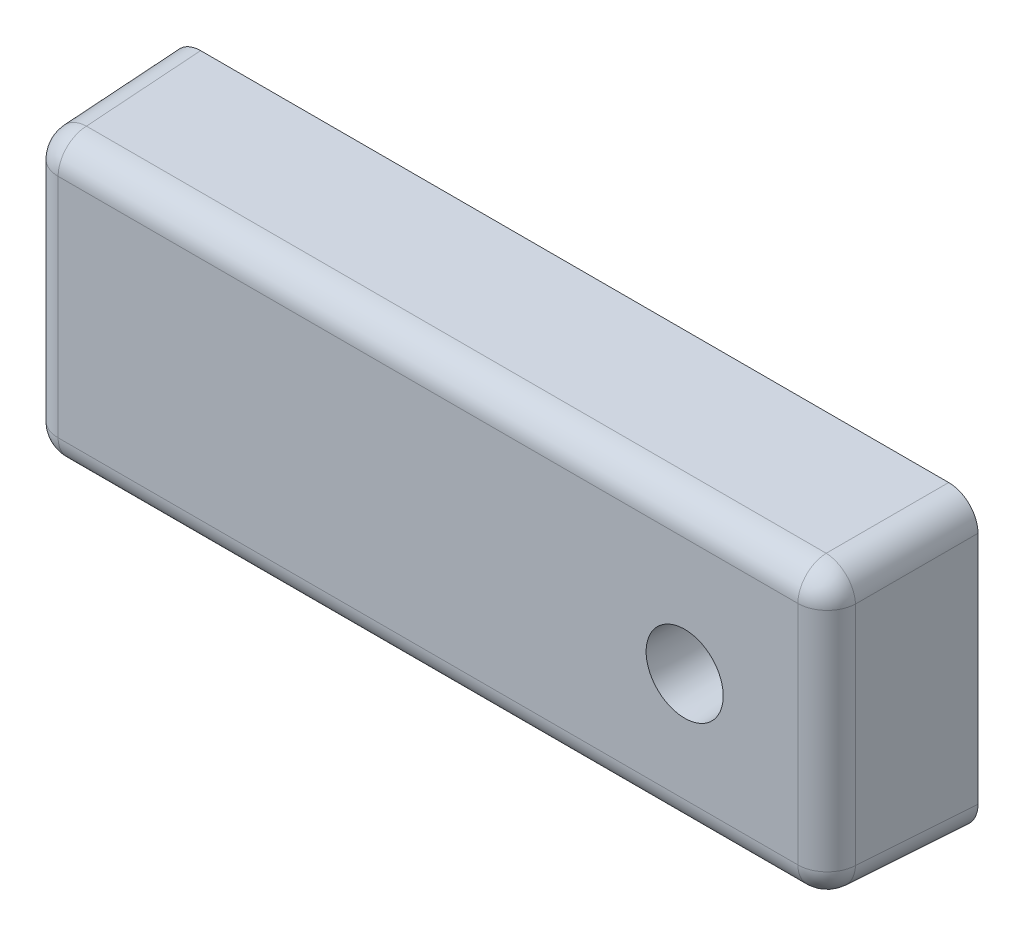
SolidWorks part; units mm, degrees
ref_plane "Front Plane" through (0, 0, 0) normal (0, 0, 1) x (1, 0, 0)
ref_plane "Top Plane" through (0, 0, 0) normal (0, 1, 0) x (1, 0, 0)
ref_plane "Right Plane" through (0, 0, 0) normal (1, 0, 0) x (0, 0, -1)
sketch "Sketch1" plane through (0, 0, 0) normal (0, 0, 1) x (1, 0, 0)
  line L1 (-13, 2.7505) -> (-68, 2.7505)
  line L2 (-13, 2.7505) -> (-13, 22.7505)
  line L3 (-13, 22.7505) -> (-68, 22.7505)
  line L4 (-68, 2.7505) -> (-68, 22.7505)
  circle A0 centre (-22.9998, 12.4582) radius 2.2792 construction
  circle A1 centre (-22.9998, 12.4582) radius 2.2792
  spline S0 degree 3 poles (-22.91, 10.1824) (-22.4605, 10.2302) (-22.1691, 10.3218) (-21.7781, 10.5356) (-21.6534, 10.6204) (-21.4236, 10.8124) (-21.3196, 10.9185) (-21.1329, 11.1504) (-21.0496, 11.2774) (-20.9115, 11.5412) (-20.8558, 11.6789) (-20.7715, 11.9661) (-20.7433, 12.1144) (-20.7165, 12.4102) (-20.7175, 12.5597) (-20.7495, 12.8588) (-20.7797, 13.0045) (-20.8679, 13.2884) (-20.9269, 13.428) (-21.0698, 13.6903) (-21.1532, 13.8133) (-21.3439, 14.0427) (-21.452, 14.1492) (-21.799, 14.4297) (-22.0699, 14.5722) (-22.4973, 14.6982) (-22.6453, 14.7267) (-22.9437, 14.7538) (-23.0923, 14.7525) (-23.3883, 14.721) (-23.5369, 14.6902) (-23.8213, 14.6014) (-23.9581, 14.5435) (-24.2207, 14.4002) (-24.3456, 14.3151) (-24.5737, 14.1248) (-24.6784, 14.0185) (-24.8673, 13.7842) (-24.9488, 13.6596) (-25.0869, 13.3965) (-25.1438, 13.2561) (-25.2281, 12.9694) (-25.2559, 12.8234) (-25.2831, 12.5265) (-25.2819, 12.3746) (-25.2347, 11.9308) (-25.144, 11.6386) (-24.8602, 11.1166) (-24.6649, 10.8811) (-24.318, 10.6003) (-24.1913, 10.5167) (-23.9276, 10.3779) (-23.79, 10.322) (-23.5034, 10.2372) (-23.3548, 10.2087) (-23.0589, 10.1815) (-22.91, 10.1824) (-22.4605, 10.2302) (-22.1691, 10.3218) knots -0.03125 -0.03125 0 0 0.0625 0.0625 0.09375 0.09375 0.125 0.125 0.15625 0.15625 0.1875 0.1875 0.21875 0.21875 0.25 0.25 0.28125 0.28125 0.3125 0.3125 0.34375 0.34375 0.375 0.375 0.4375 0.4375 0.46875 0.46875 0.5 0.5 0.53125 0.53125 0.5625 0.5625 0.59375 0.59375 0.625 0.625 0.65625 0.65625 0.6875 0.6875 0.71875 0.71875 0.75 0.75 0.8125 0.8125 0.875 0.875 0.90625 0.90625 0.9375 0.9375 0.96875 0.96875 1 1 1.0625 1.0625 1.09375 only from (-22.7602, 10.1984) to (-22.7602, 10.1984) construction
  dimension "D1" = 9.7602
  dimension "D2" = 7.4479
  dimension "D3" = 20
  dimension "D4" = 55
  dimension "D5" = 9.7077
  dimension "D6" = 9.9998
extrude "Boss-Extrude1" add sketch "Sketch1" along normal blind 10 draft 2
fillet "Fillet1" radius 2 4 edges at (-40.5, 3.0997, 10) (-67.6508, 12.7505, 10) (-40.5, 22.4013, 10) (-13.3492, 12.7505, 10)
fillet "Fillet2" radius 2 8 edges at (-13.8913, 21.8592, 9.4387) (-67.1087, 21.8592, 9.4387) (-13.8913, 3.6417, 9.4387) (-67.1087, 3.6417, 9.4387) (-13.1409, 22.6096, 4.0349) (-67.8591, 22.6096, 4.0349) (-13.1409, 2.8914, 4.0349) (-67.8591, 2.8914, 4.0349)
scale "Scale1"
other "Parting Line2"
other "Shut-Off Surface2"
other "Parting Surface2" parameters "D1"=42.2
sketch "Sketch3" plane through (0, 0, -2.453) normal (0, 0, -1) x (-1, 0, 0)
  line L1 (96.8339, -29.4991) -> (-15.2623, -29.4991)
  line L2 (96.8339, -29.4991) -> (96.8339, 58.6404)
  line L3 (96.8339, 58.6404) -> (-15.2623, 58.6404)
  line L4 (-15.2623, -29.4991) -> (-15.2623, 58.6404)
  line L5 (96.8339, -29.4991) -> (-15.2623, 58.6404) construction
  line L6 (96.8339, 58.6404) -> (-15.2623, -29.4991) construction
  point P0 (40.7858, 14.5707)
  dimension "D1" = 88.1396
  dimension "D2" = 112.0961
other "Tooling Split1" parameters "D1"=50, "D2"=11, "D3"=3
